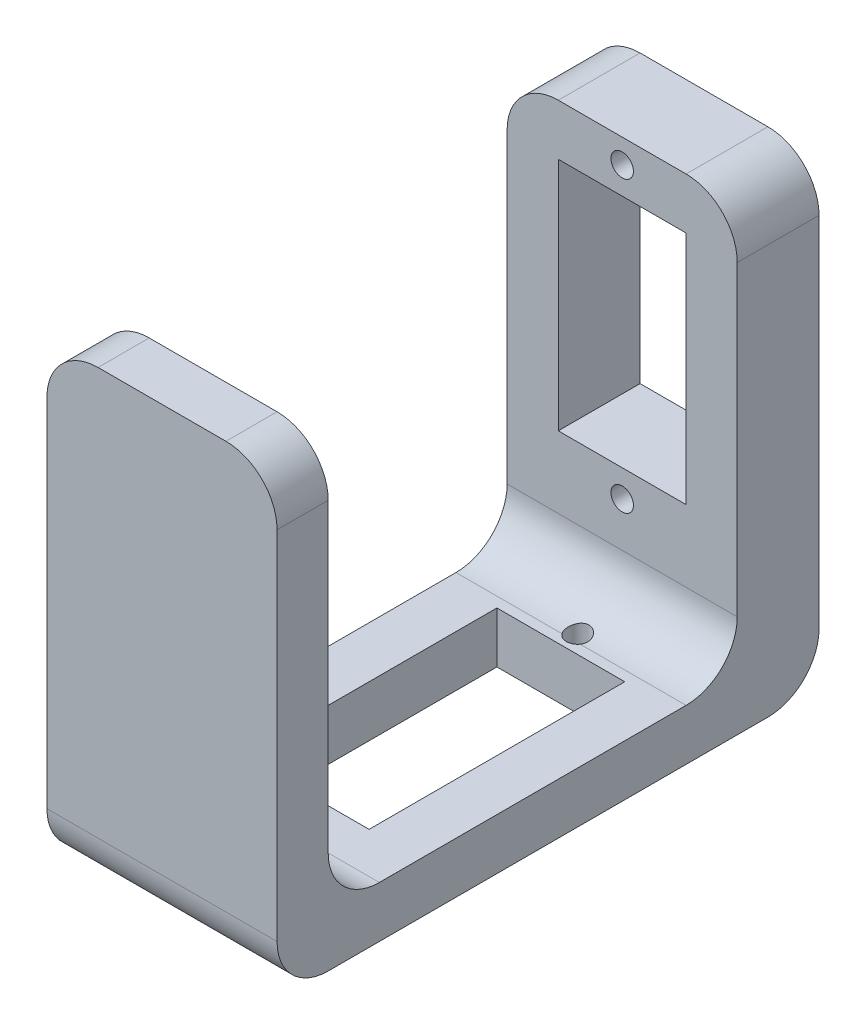
SolidWorks part; units mm, degrees
ref_plane "Ön Düzlem" through (0, 0, 0) normal (0, 0, 1) x (1, 0, 0)
ref_plane "Üst Düzlem" through (0, 0, 0) normal (0, 1, 0) x (1, 0, 0)
ref_plane "Sağ Düzlem" through (0, 0, 0) normal (1, 0, 0) x (0, 0, -1)
sketch "Sketch1" plane through (0, 0, 0) normal (0, 0, 1) x (1, 0, 0)
  line L0 (-11.25, 16.5) -> (11.25, 16.5)
  line L1 (-6.25, 11.5) -> (6.25, 11.5)
  line L2 (-6.25, 11.5) -> (-6.25, -11.5)
  line L3 (-6.25, -11.5) -> (6.25, -11.5)
  line L4 (6.25, 11.5) -> (6.25, -11.5)
  line L5 (-6.25, 11.5) -> (6.25, -11.5) construction
  line L6 (-6.25, -11.5) -> (6.25, 11.5) construction
  line L7 (11.25, 16.5) -> (11.25, -16.5)
  line L8 (-11.25, -16.5) -> (11.25, -16.5)
  line L9 (-11.25, 16.5) -> (-11.25, -16.5)
  point P0 (0, 0)
  dimension "D1" = 12.5
  dimension "D2" = 23
  dimension "D3" = 5
extrude "Boss-Extrude1" add sketch "Sketch1" along normal blind 8
sketch "Sketch2" plane through (0, 0, 8) normal (0, 0, 1) x (1, 0, 0)
  circle A0 centre (0, -14.1452) radius 1.1
  circle A1 centre (0, 14.1452) radius 1.1
extrude "Cut-Extrude1" cut sketch "Sketch2" against normal through all
sketch "Sketch4" plane through (0, 0, 0) normal (0, 0, -1) x (-1, 0, 0)
  line L0 (-11.25, -16.5) -> (11.25, -16.5)
  line L1 (-11.25, -16.5) -> (-11.25, -28.5)
  line L2 (11.25, -16.5) -> (11.25, -28.5)
  line L3 (-11.25, -28.5) -> (11.25, -28.5)
  dimension "D1" = 12
extrude "Boss-Extrude3" add sketch "Sketch4" against normal up to surface (8 mm away) up to face at (1.1, -14.1452, 8)
sketch "Sketch5" plane through (0, 0, 8) normal (0, 0, 1) x (1, 0, 0)
  line L0 (-11.25, -28.5) -> (11.25, -28.5)
  line L1 (-11.25, -28.5) -> (-11.25, -23.5)
  line L2 (11.25, -28.5) -> (11.25, -23.5)
  line L3 (-11.25, -23.5) -> (11.25, -23.5)
  dimension "D1" = 5
extrude "Boss-Extrude4" add sketch "Sketch5" along normal blind 45
sketch "Sketch6" plane through (0, -28.5, 0) normal (0, -1, 0) x (1, 0, 0)
  line L0 (-11.25, 53) -> (11.25, 53) construction
  line L1 (-6.25, 14) -> (6.25, 14)
  line L2 (-6.25, 14) -> (-6.25, 39)
  line L3 (-6.25, 39) -> (6.25, 39)
  line L4 (6.25, 14) -> (6.25, 39)
  line L5 (-6.25, 14) -> (6.25, 39) construction
  line L6 (-6.25, 39) -> (6.25, 14) construction
  line L7 (-11.25, 53) -> (-11.25, 0) construction
  point P0 (0, 26.5)
  point P8 (0, 53)
  point P12 (-11.25, 26.5)
  dimension "D1" = 12.5
  dimension "D2" = 25
extrude "Cut-Extrude2" cut sketch "Sketch6" against normal through all
sketch "Sketch7" plane through (0, -28.5, 0) normal (0, -1, 0) x (1, 0, 0)
  circle A0 centre (0, 40.6452) radius 1.1
  circle A1 centre (0, 12.3548) radius 1.1
extrude "Cut-Extrude3" cut sketch "Sketch7" against normal blind 65
fillet "Fillet1" radius 5 1 edges at (0, -23.5, 8)
ref_plane "Plane1" through (-11.25, -23.5, 53) normal (-1, 0, 0) x (0, 0, 1)
sketch "Sketch9" plane through (0, 0, 53) normal (0, 0, 1) x (1, 0, 0)
  line L0 (-11.25, -28.5) -> (11.25, -28.5)
  line L1 (-11.25, -28.5) -> (-11.25, 16.3656)
  line L2 (11.25, -28.5) -> (11.25, 16.3656)
  line L3 (-11.25, 16.3656) -> (11.25, 16.3656)
extrude "Boss-Extrude5" add sketch "Sketch9" against normal blind 5
sketch "Sketch10" plane through (0, 0, 48) normal (0, 0, -1) x (-1, 0, 0)
  circle A0 centre (0, 5) radius 8.7365
extrude "Cut-Extrude4" cut sketch "Sketch10" against normal blind 3
fillet "Fillet2" radius 5 1 edges at (0, -23.5, 48)
fillet "Fillet3" radius 5 2 edges at (0, -28.5, 0) (0, -28.5, 53)
fillet "Fillet4" radius 5 4 edges at (11.25, 16.3656, 50.5) (-11.25, 16.3656, 50.5) (-11.25, 16.5, 4) (11.25, 16.5, 4)
